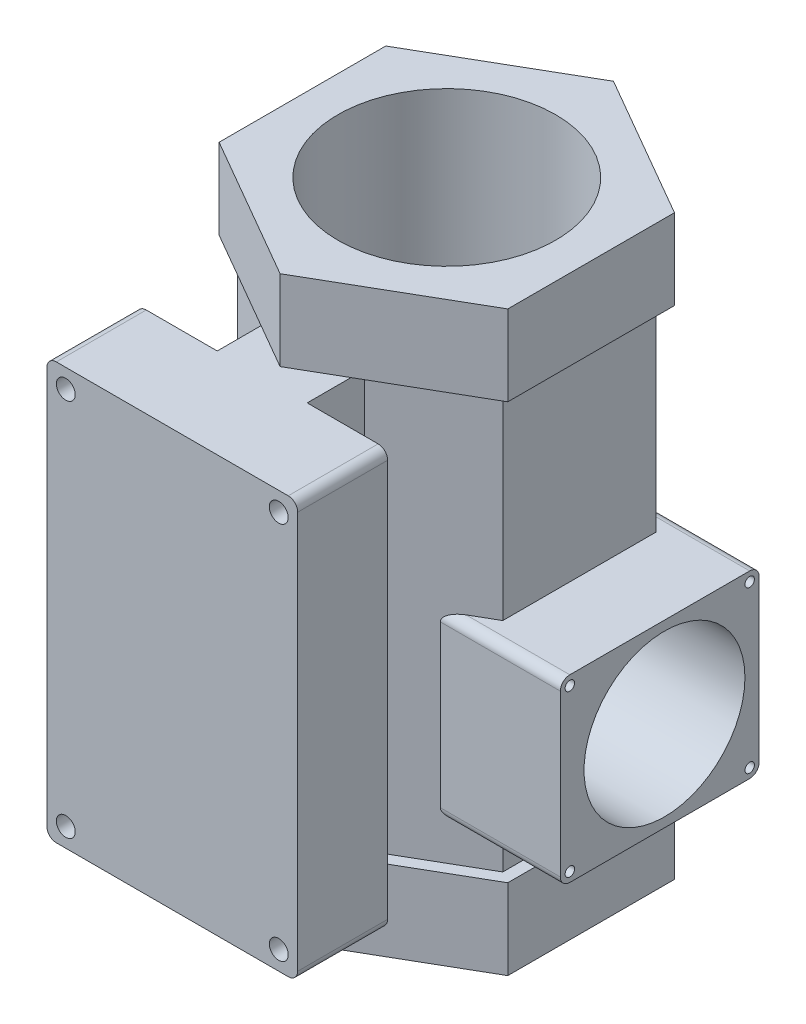
SolidWorks part; units mm, degrees
ref_plane "Спереди" through (0, 0, 0) normal (0, 0, 1) x (1, 0, 0)
ref_plane "Сверху" through (0, 0, 0) normal (0, 1, 0) x (1, 0, 0)
ref_plane "Справа" through (0, 0, 0) normal (1, 0, 0) x (0, 0, -1)
sketch "Эскиз центра" plane through (0, 0, 0) normal (0, 1, 0) x (1, 0, 0)
  line L0 (0, 0) -> (0, -290) construction
  line L1 (0, 161.6581) -> (-140, 80.829)
  line L2 (-140, 80.829) -> (-140, -80.829)
  line L3 (-140, -80.829) -> (-47.5, -134.2339)
  line L4 (47.5, -134.2339) -> (140, -80.829)
  line L5 (140, -80.829) -> (140, 80.829)
  line L6 (140, 80.829) -> (0, 161.6581)
  line L7 (132.5, -290) -> (-132.5, -290)
  line L8 (-132.5, -290) -> (-132.5, -195)
  line L9 (-132.5, -195) -> (-47.5, -195)
  line L10 (-47.5, -195) -> (-47.5, -134.2339)
  line L11 (47.5, -195) -> (47.5, -134.2339)
  line L12 (132.5, -195) -> (47.5, -195)
  line L13 (132.5, -290) -> (132.5, -195)
  circle A0 centre (0, 0) radius 140 construction
  dimension "D1" = 280
  dimension "D2" = 95
  dimension "D3" = 265
  dimension "D4" = 95
  dimension "D5" = 290
sketch "Эскиз2" plane through (0, 0, 0) normal (0, 1, 0) x (1, 0, 0)
  line L1 (0, 176.0918) -> (-152.5, 88.0459)
  line L2 (-152.5, 88.0459) -> (-152.5, -88.0459)
  line L3 (-152.5, -88.0459) -> (0, -176.0918)
  line L4 (0, -176.0918) -> (152.5, -88.0459)
  line L5 (152.5, -88.0459) -> (152.5, 88.0459)
  line L6 (152.5, 88.0459) -> (0, 176.0918)
  circle A0 centre (0, 0) radius 152.5 construction
  dimension "D1" = 305
extrude "Боковой многогранник 1" add sketch "Эскиз2" along normal blind 85
extrude "Центральная часть" add sketch "Эскиз центра" against normal blind 440
sketch "Эскиз4" plane through (0, -440, 0) normal (0, -1, 0) x (1, 0, 0)
  line L1 (0, -176.0918) -> (152.5, -88.0459)
  line L2 (152.5, -88.0459) -> (152.5, 88.0459)
  line L3 (152.5, 88.0459) -> (0, 176.0918)
  line L4 (0, 176.0918) -> (-152.5, 88.0459)
  line L5 (-152.5, 88.0459) -> (-152.5, -88.0459)
  line L6 (-152.5, -88.0459) -> (0, -176.0918)
  circle A0 centre (0, 0) radius 152.5 construction
extrude "Боковой многогранник 2" add sketch "Эскиз4" along normal blind 85
sketch "Эскиз5" plane through (0, 85, 0) normal (0, 1, 0) x (1, 0, 0)
  circle A0 centre (0, 0) radius 115
  dimension "D1" = 230
sketch "Эскиз10" plane through (140, 0, 0) normal (1, 0, 0) x (0, 0, -1)
  line L0 (88.0459, -525) -> (-88.0459, -525) construction
  line L2 (-105, -210) -> (105, -210)
  line L3 (-105, -210) -> (-105, -400)
  line L4 (-105, -400) -> (105, -400)
  line L5 (105, -210) -> (105, -400)
  line L6 (-105, -210) -> (105, -400) construction
  line L7 (-105, -400) -> (105, -210) construction
  point P0 (0, -305)
  dimension "D1" = 190
  dimension "D2" = 210
  dimension "D3" = 220
  dimension "D4" = 125
extrude "Боковой фланц" add sketch "Эскиз10" along normal blind 85 and the other way blind 140
extrude "Центральный вырез" cut sketch "Эскиз5" against normal through all contours A0
sketch "Эскиз12" plane through (225, 0, 0) normal (1, 0, 0) x (0, 0, -1)
  line L0 (-290, -440) -> (-290, 0) construction
  circle A0 centre (5, -305) radius 85
  dimension "D1" = 170
  dimension "D2" = 295
extrude "Боковой вырез" cut sketch "Эскиз12" against normal up to next
sketch "Эскиз13" plane through (0, 0, 290) normal (0, 0, 1) x (1, 0, 0)
  line L0 (132.5, -440) -> (132.5, 0) construction
  line L1 (-132.5, 0) -> (132.5, 0) construction
  line L2 (-132.5, -440) -> (-132.5, 0) construction
  line L3 (-132.5, -440) -> (132.5, -440) construction
  circle A0 centre (-112.5, -420) radius 10
  circle A1 centre (112.5, -420) radius 10
  circle A2 centre (-112.5, -20) radius 10
  circle A3 centre (112.5, -20) radius 10
  dimension "D1" = 20
  dimension "D5" = 20
  dimension "D6" = 20
  dimension "D7" = 20
  dimension "D8" = 20
  dimension "D2" = 20
  dimension "D3" = 20
  dimension "D4" = 20
  dimension "D9" = 20
  dimension "D10" = 20
  dimension "D11" = 20
  dimension "D12" = 20
extrude "Отверстия в основании" cut sketch "Эскиз13" against normal up to next
sketch "Эскиз14" plane through (225, 0, 0) normal (1, 0, 0) x (0, 0, -1)
  line L0 (-105, -210) -> (-105, -400) construction
  line L1 (105, -210) -> (-105, -210) construction
  line L2 (105, -400) -> (105, -210) construction
  line L3 (-105, -400) -> (105, -400) construction
  line L4 (105, -400) -> (105, -210) construction
  circle A0 centre (95, -220) radius 5
  circle A1 centre (95, -390) radius 5
  circle A2 centre (-95, -220) radius 5
  circle A3 centre (-95, -390) radius 5
  dimension "D1" = 10
  dimension "D9" = 10
  dimension "D10" = 10
  dimension "D11" = 10
  dimension "D12" = 10
  dimension "D2" = 10
  dimension "D3" = 10
  dimension "D4" = 10
  dimension "D5" = 10
  dimension "D6" = 10
  dimension "D7" = 10
  dimension "D8" = 10
extrude "Вырез-Вытянуть6" cut sketch "Эскиз14" against normal blind 30
fillet "Скругление2" radius 10 4 edges at (-132.5, -440, 242.5) (132.5, -440, 242.5) (-132.5, 0, 242.5) (132.5, 0, 242.5)
fillet "Скругление3" radius 10 4 edges at (161.5673, -210, -105) (161.5673, -400, -105) (161.5673, -400, 105) (161.5673, -210, 105)
